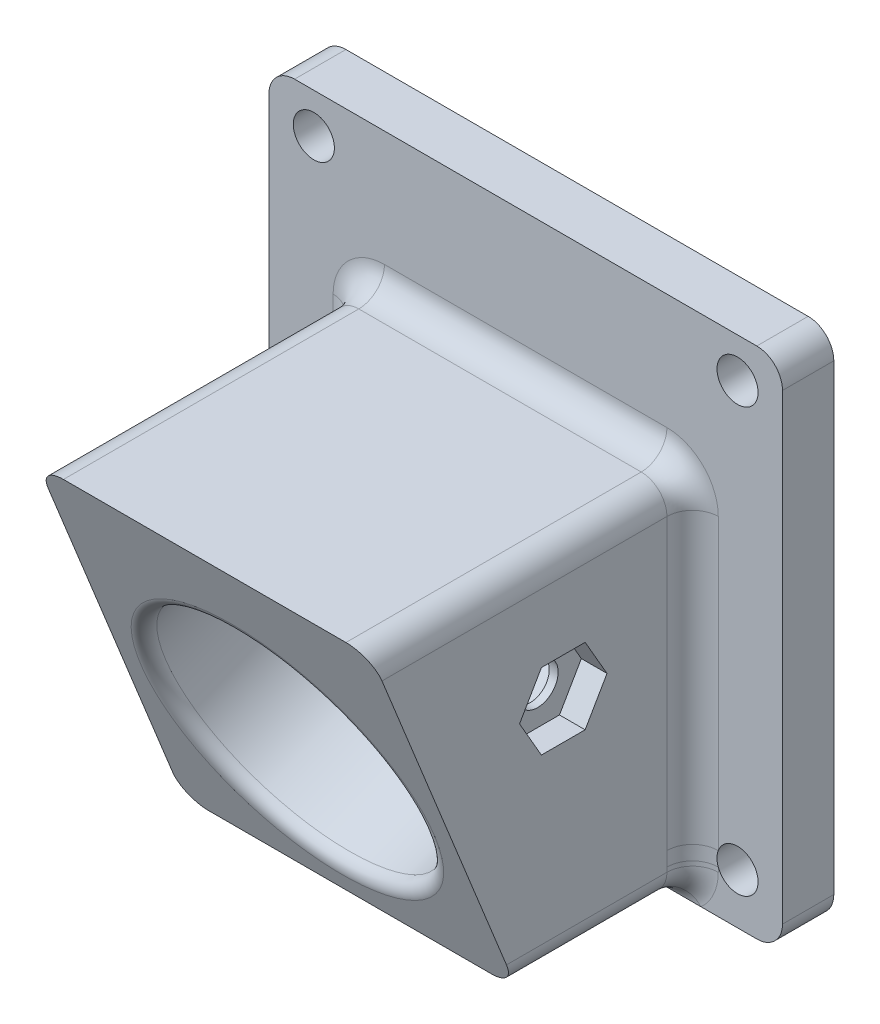
SolidWorks part; units mm, degrees
ref_plane "Front Plane" through (0, 0, 0) normal (0, 0, 1) x (1, 0, 0)
ref_plane "Top Plane" through (0, 0, 0) normal (0, 1, 0) x (1, 0, 0)
ref_plane "Right Plane" through (0, 0, 0) normal (1, 0, 0) x (0, 0, -1)
sketch "Sketch1" plane through (0, 0, 0) normal (0, 0, 1) x (1, 0, 0)
  line L0 (-20, 20) -> (20, -20) construction
  line L1 (-20, 20) -> (20, 20)
  line L2 (-20, 20) -> (-20, -20)
  line L3 (-20, -20) -> (20, -20)
  line L4 (20, 20) -> (20, -20)
  line L5 (-16.5, 16.0909) -> (16.5, -16.0909) construction
  line L6 (-16.5, 16.9091) -> (16.5, 16.9091) construction
  line L7 (-16.5, 16.9091) -> (-16.5, -16.0909) construction
  line L8 (-16.5, -16.0909) -> (16.5, -16.0909) construction
  line L9 (16.5, 16.9091) -> (16.5, -16.0909) construction
  circle A0 centre (-16.5, 16.9091) radius 1.6
  circle A1 centre (16.5, 16.9091) radius 1.6
  circle A2 centre (16.5, -16.0909) radius 1.6
  circle A3 centre (-16.5, -16.0909) radius 1.6
  point P4 (0, 0)
  point P11 (0, 0)
  dimension "D3" = 3.2
  dimension "D1" = 40
  dimension "D2" = 33
extrude "Boss-Extrude1" add sketch "Sketch1" along normal blind 4
fillet "Fillet1" radius 2 4 edges at (-20, -20, 2) (20, -20, 2) (20, 20, 2) (-20, 20, 2)
sketch "Sketch2" plane through (0, 0, 4) normal (0, 0, 1) x (1, 0, 0)
  line L1 (0, -19) -> (0, -20) construction
  line L2 (-13, 7) -> (-13, -19)
  line L3 (-13, -19) -> (13, -19)
  line L4 (13, 7) -> (13, -19)
  line L5 (-13, 7) -> (13, 7) construction
  line L6 (13, 7) -> (-13, 7) construction
  line L7 (-13, 7) -> (-13, 9)
  line L8 (-13, 9) -> (13, 9)
  line L9 (13, 7) -> (13, 9)
  line L10 (-18, -20) -> (18, -20) construction
  dimension "D1" = 26
  dimension "D2" = 1
  dimension "D3" = 2
extrude "Boss-Extrude2" add sketch "Sketch2" along normal blind 25
sketch "Sketch4" plane through (-13, 0, 0) normal (-1, 0, 0) x (0, 0, 1)
  line L0 (29, -19) -> (17.6873, -19)
  line L1 (29, -19) -> (4, -19) construction
  line L2 (17.6873, -19) -> (29, 9)
  line L3 (29, 9) -> (29, -19)
  dimension "D1" = 22
extrude "Cut-Extrude1" cut sketch "Sketch4" against normal through all
sketch "Sketch5" plane through (0, -8.8096, 21.8045) normal (0, -0.3746, 0.9272) x (1, 0, 0)
  line L0 (13, 19.2082) -> (13, -10.9907) construction
  line L1 (-13, -10.9907) -> (13, -10.9907) construction
  line L2 (-13, -10.9907) -> (-13, 15.0093) construction
  line L3 (-13, 15.0093) -> (13, 15.0093) construction
  line L4 (13, -10.9907) -> (13, 15.0093) construction
  line L5 (-13, 15.0093) -> (13, -10.9907) construction
  line L6 (0, 2.0093) -> (0, -10.9907) construction
  circle A0 centre (0, 2.0093) radius 10.4
  dimension "D1" = 20.8
extrude "Cut-Extrude2" cut sketch "Sketch5" against normal blind 16.65
sketch "Sketch6" plane through (-13, 0, 0) normal (-1, 0, 0) x (0, 0, 1)
  line L0 (23.3436, -5) -> (14.0718, -1.2539) construction
  line L1 (29, 9) -> (17.6873, -19) construction
  circle A0 centre (14.0718, -1.2539) radius 1.6
  dimension "D2" = 3.2
  dimension "D1" = 10
extrude "Cut-Extrude3" cut sketch "Sketch6" against normal through all
sketch "Sketch7" plane through (-13, 0, 0) normal (-1, 0, 0) x (0, 0, 1)
  line L0 (14.0718, -1.2539) -> (12.4718, -1.2539) construction
  circle A0 centre (14.0718, -1.2539) radius 1.6 construction
  circle A1 centre (14.0718, -1.2539) radius 3
  dimension "D1" = 6
extrude "Cut-Extrude4" cut sketch "Sketch7" against normal blind 2
sketch "Sketch8" plane through (13, 0, 0) normal (1, 0, 0) x (0, 0, -1)
  line L1 (-10.6654, -1.2539) -> (-12.3686, 1.6961)
  line L2 (-12.3686, 1.6961) -> (-15.775, 1.6961)
  line L3 (-15.775, 1.6961) -> (-17.4782, -1.2539)
  line L4 (-17.4782, -1.2539) -> (-15.775, -4.2039)
  line L5 (-15.775, -4.2039) -> (-12.3686, -4.2039)
  line L6 (-12.3686, -4.2039) -> (-10.6654, -1.2539)
  circle A0 centre (-14.0718, -1.2539) radius 2.95 construction
  dimension "D1" = 5.9
extrude "Cut-Extrude5" cut sketch "Sketch8" against normal blind 2
fillet "Fillet2" radius 2 4 edges at (-13, 9, 16.5) (-13, -19, 10.8436) (13, -19, 10.8436) (13, 9, 16.5)
fillet "Fillet3" radius 2 7 edges at (-12.4142, 8.4142, 4) (0, 9, 4) (12.4142, 8.4142, 4) (13, -5, 4) (12.4142, -18.4142, 4) (-12.4142, -18.4142, 4) (-13, -5, 4)
fillet "Fillet4" radius 1 1 edges at (0, -16.5893, 18.6612)
